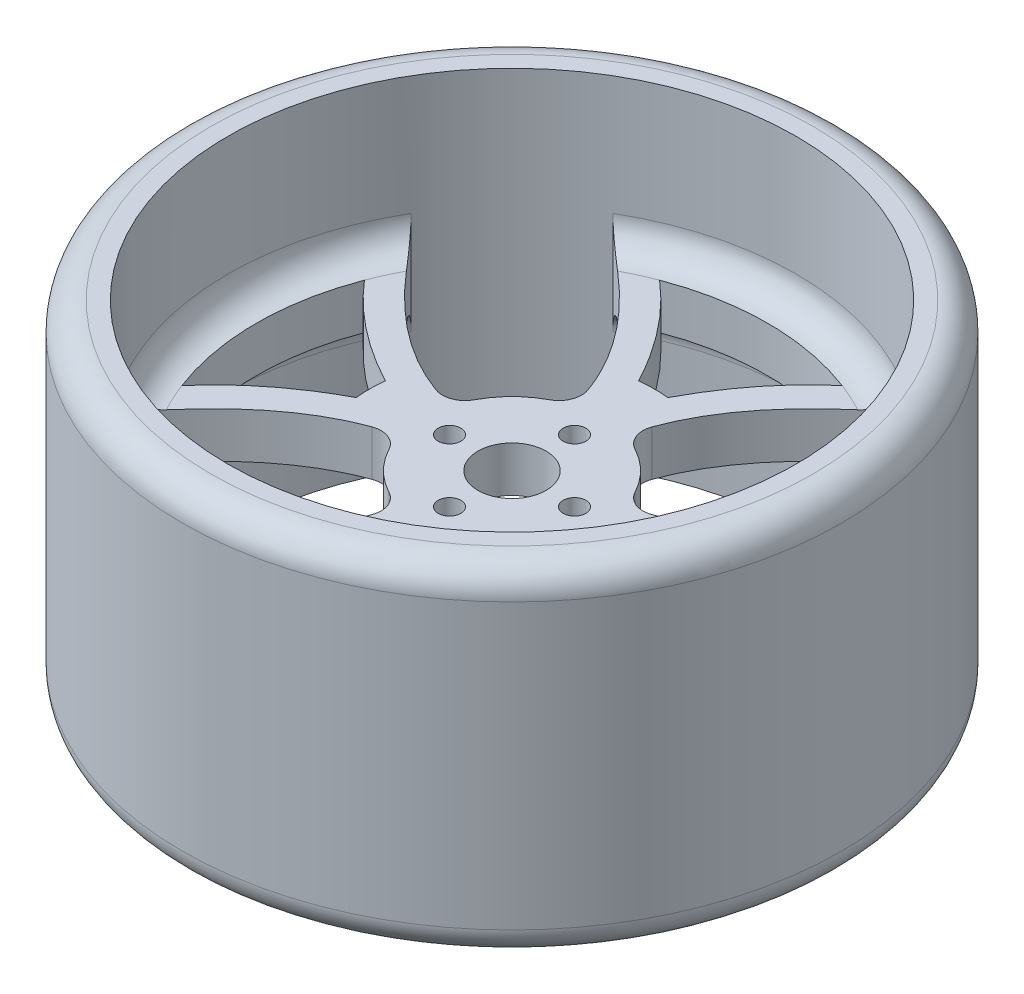
SolidWorks part; units mm, degrees
ref_plane "Front Plane" through (0, 0, 0) normal (0, 0, 1) x (1, 0, 0)
ref_plane "Top Plane" through (0, 0, 0) normal (0, 1, 0) x (1, 0, 0)
ref_plane "Right Plane" through (0, 0, 0) normal (1, 0, 0) x (0, 0, -1)
sketch "Sketch1" plane through (0, 0, 0) normal (0, 1, 0) x (1, 0, 0)
  circle A0 centre (0, 0) radius 3
  circle A1 centre (0, 0) radius 8
  dimension "D1" = 6
  dimension "D2" = 16
extrude "Boss-Extrude1" add sketch "Sketch1" along normal mid plane 4
sketch "Sketch2" plane through (0, 0, 0) normal (0, 1, 0) x (1, 0, 0)
  line L0 (0, 25) -> (0, -25) construction
  line L1 (-25, 0) -> (25, 0) construction
  arc A2 (2.2696, 7.6713) -> (-2.2696, 7.6713) centre (0, 0) ccw
  arc A3 (12.6709, 21.5511) -> (-12.6709, 21.5511) centre (0, 0) ccw
  circle A4 centre (0, 0) radius 25 construction
  arc A5 (7.6713, -2.2696) -> (7.6713, 2.2696) centre (0, 0) ccw
  arc A6 (21.5511, -12.6709) -> (21.5511, 12.6709) centre (0, 0) ccw
  arc A7 (-2.2696, -7.6713) -> (2.2696, -7.6713) centre (0, 0) ccw
  arc A8 (-12.6709, -21.5511) -> (12.6709, -21.5511) centre (0, 0) ccw
  arc A9 (-7.6713, 2.2696) -> (-7.6713, -2.2696) centre (0, 0) ccw
  arc A10 (-21.5511, 12.6709) -> (-21.5511, -12.6709) centre (0, 0) ccw
  circle A11 centre (0, 0) radius 22.5 construction
  circle A12 centre (0, 0) radius 12.5 construction
  arc A14 (1.2819, 12.4341) -> (-1.2819, 12.4341) centre (0, 0) ccw
  arc A15 (8.0302, 21.0182) -> (-8.0302, 21.0182) centre (0, 0) ccw
  arc A16 (21.0182, -8.0302) -> (21.0182, 8.0302) centre (0, 0) ccw
  arc A17 (12.4341, -1.2819) -> (12.4341, 1.2819) centre (0, 0) ccw
  arc A18 (-8.0302, -21.0182) -> (8.0302, -21.0182) centre (0, 0) ccw
  arc A19 (-1.2819, -12.4341) -> (1.2819, -12.4341) centre (0, 0) ccw
  arc A20 (-21.0182, 8.0302) -> (-21.0182, -8.0302) centre (0, 0) ccw
  arc A21 (-12.4341, 1.2819) -> (-12.4341, -1.2819) centre (0, 0) ccw
  spline S0 degree 2 poles (-12.6709, 21.5511) (-4.0139, 15.0092) (-2.2696, 7.6713) knots 0 0 0 0.242244 0.242244 0.242244
  spline S1 degree 2 poles (12.6709, 21.5511) (4.0139, 15.0092) (2.2696, 7.6713) knots 0 0 0 0.242244 0.242244 0.242244
  spline S2 degree 2 poles (21.5511, 12.6709) (15.0092, 4.0139) (7.6713, 2.2696) knots 0 0 0 0.242244 0.242244 0.242244
  spline S3 degree 2 poles (21.5511, -12.6709) (15.0092, -4.0139) (7.6713, -2.2696) knots 0 0 0 0.242244 0.242244 0.242244
  spline S4 degree 2 poles (12.6709, -21.5511) (4.0139, -15.0092) (2.2696, -7.6713) knots 0 0 0 0.242244 0.242244 0.242244
  spline S5 degree 2 poles (-12.6709, -21.5511) (-4.0139, -15.0092) (-2.2696, -7.6713) knots 0 0 0 0.242244 0.242244 0.242244
  spline S6 degree 2 poles (-21.5511, -12.6709) (-15.0092, -4.0139) (-7.6713, -2.2696) knots 0 0 0 0.242244 0.242244 0.242244
  spline S7 degree 2 poles (-21.5511, 12.6709) (-15.0092, 4.0139) (-7.6713, 2.2696) knots 0 0 0 0.242244 0.242244 0.242244
  spline S8 degree 2 poles (1.2819, 12.4341) (3.9986, 17.5696) (8.0302, 21.0182) knots 0 0 0 0.407977 0.407977 0.407977
  spline S9 degree 2 poles (-1.2819, 12.4341) (-3.9986, 17.5696) (-8.0302, 21.0182) knots 0 0 0 0.407977 0.407977 0.407977
  spline S10 degree 2 poles (12.4341, 1.2819) (17.5696, 3.9986) (21.0182, 8.0302) knots 0 0 0 0.407977 0.407977 0.407977
  spline S11 degree 2 poles (12.4341, -1.2819) (17.5696, -3.9986) (21.0182, -8.0302) knots 0 0 0 0.407977 0.407977 0.407977
  spline S12 degree 2 poles (1.2819, -12.4341) (3.9986, -17.5696) (8.0302, -21.0182) knots 0 0 0 0.407977 0.407977 0.407977
  spline S13 degree 2 poles (-1.2819, -12.4341) (-3.9986, -17.5696) (-8.0302, -21.0182) knots 0 0 0 0.407977 0.407977 0.407977
  spline S14 degree 2 poles (-12.4341, -1.2819) (-17.5696, -3.9986) (-21.0182, -8.0302) knots 0 0 0 0.407977 0.407977 0.407977
  spline S15 degree 2 poles (-12.4341, 1.2819) (-17.5696, 3.9986) (-21.0182, 8.0302) knots 0 0 0 0.407977 0.407977 0.407977
  point P27 (0, 0)
  point P46 (0, 0)
  dimension "D1" = 8
  dimension "D2" = 25
  dimension "D3" = 17.6933
  dimension "D5" = 45
  dimension "D6" = 25
  dimension "D7" = 17.6933
  dimension "D4" = 4
  dimension "D8" = 4
extrude "Boss-Extrude2" add sketch "Sketch2" along normal mid plane 4
sketch "Sketch3" plane through (0, 0, 0) normal (0, 1, 0) x (1, 0, 0)
  circle A0 centre (0, 0) radius 25
  circle A1 centre (0, 0) radius 29
  dimension "D2" = 58
  dimension "D3" = 50
extrude "Boss-Extrude3" add sketch "Sketch3" along normal mid plane 30
fillet "Fillet4" radius 2 8 edges at (2.2696, 0, -7.6713) (7.6713, 0, -2.2696) (2.2696, 0, 7.6713) (7.6713, 0, 2.2696) (-2.2696, 0, 7.6713) (-7.6713, 0, 2.2696) (-7.6713, 0, -2.2696) (-2.2696, 0, -7.6713)
fillet "Fillet5" radius 2.5 4 edges at (0, 2, 25) (25, 2, 0) (0, 2, -25) (-25, 2, 0)
fillet "Fillet6" radius 2.5 4 edges at (0, -2, -25) (-25, -2, 0) (0, -2, 25) (25, -2, 0)
fillet "Fillet7" radius 2.5 2 edges at (0, -15, 29) (0, 15, 29)
sketch "Sketch4" plane through (0, 0, 0) normal (0, 1, 0) x (1, 0, 0)
  circle A0 centre (0, 0) radius 3 construction
  circle A1 centre (0, 0) radius 8 construction
  circle A2 centre (0, 0) radius 5.5 construction
  circle A3 centre (0, 5.5) radius 1
  circle A4 centre (5.5, 0) radius 1
  circle A5 centre (0, -5.5) radius 1
  circle A6 centre (-5.5, 0) radius 1
  point P16 (0, 0)
  dimension "D1" = 2.5
  dimension "D2" = 2
  dimension "D3" = 4
extrude "Cut-Extrude1" cut sketch "Sketch4" against normal mid plane 4
